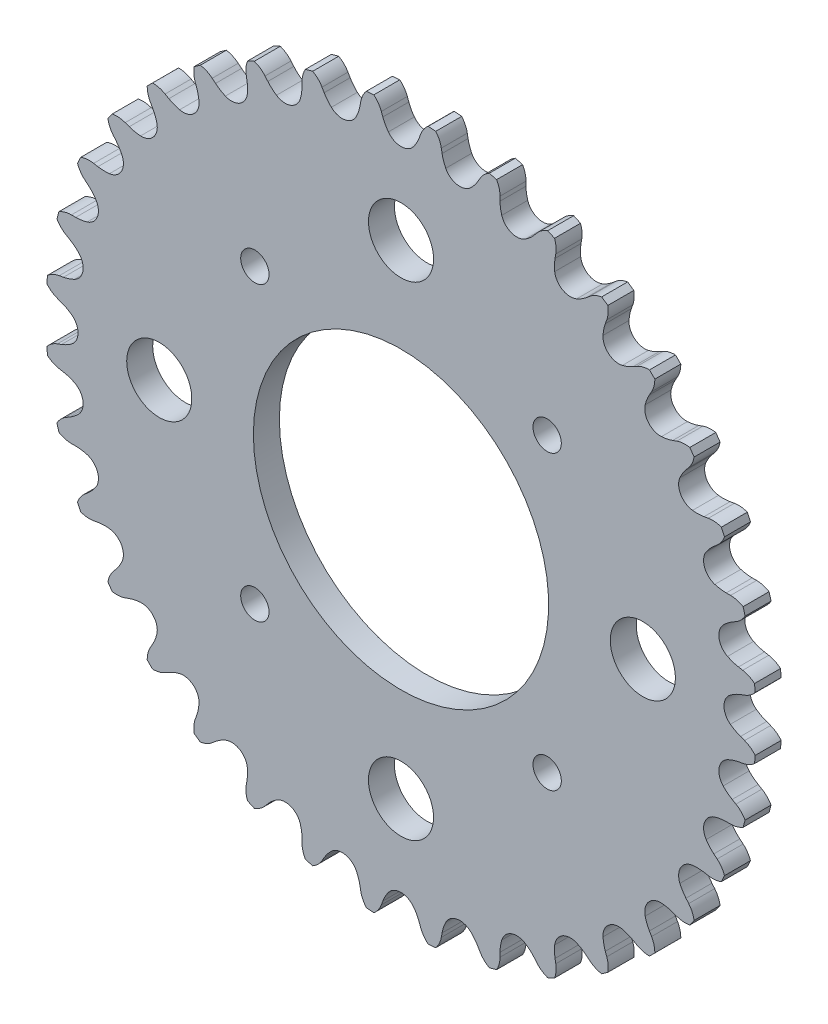
SolidWorks part; units mm, degrees
ref_plane "Front Plane" through (0, 0, 0) normal (0, 0, 1) x (1, 0, 0)
ref_plane "Top Plane" through (0, 0, 0) normal (0, 1, 0) x (1, 0, 0)
ref_plane "Right Plane" through (0, 0, 0) normal (1, 0, 0) x (0, 0, -1)
ref_axis "Axis1" through (0, 0, -88.99) along (0, 0, 1)
sketch "Sprocket-BaseSketch" plane through (0, 0, 0) normal (1, 0, 0) x (0, 0, -1)
  line L0 (1.397, 0) -> (1.397, 35.0204)
  line L1 (0.6032, 38.1954) -> (-0.6032, 38.1954)
  line L4 (-1.397, 35.0204) -> (-1.397, 0)
  line L5 (-1.397, 0) -> (1.397, 0)
  line L6 (5.588, 0) -> (-1.7463, 0) construction
  line L7 (-1.397, 35.0204) -> (-1.397, 38.1954)
  line L8 (-1.397, 38.1954) -> (-0.6032, 38.1954)
  line L9 (0.6032, 38.1954) -> (1.397, 38.1954)
  line L10 (1.397, 38.1954) -> (1.397, 35.0204)
  dimension "Hub Surface" = 1.397
  dimension "RightSide (1)" = 0.7938
  dimension "RightSide (2)" = 3.175
  dimension "LeftSide (1)" = 0.7938
  dimension "LeftSide (2)" = 3.175
  dimension "Tooth Width" = 2.794
revolve "25 (04C) ANSI (ISO) Chain Number, 2.868in P.D." add sketch "Sprocket-BaseSketch" angle 360 about L6
sketch "Tooth-Sketch" plane through (0, 0, 0) normal (0, 0, 1) x (1, 0, 0)
  line L0 (0, 0) -> (0, 48.5721) construction
  line L1 (1.9526, 36.5067) -> (2.1137, 36.9439)
  line L2 (-1.9526, 36.5067) -> (-2.1137, 36.9439)
  line L3 (0, 36.429) -> (6.3258, 35.8756) construction
  line L4 (0, 36.429) -> (-6.3258, 35.8756) construction
  arc A0 (-1.3615, 35.4154) -> (1.3615, 35.4154) centre (0, 36.429) ccw
  arc A1 (1.3615, 35.4154) -> (1.9526, 36.5067) centre (-2.1189, 38.0065) ccw
  arc A2 (-1.3615, 35.4154) -> (-1.9526, 36.5067) centre (2.1189, 38.0065) cw
  arc A3 (2.1137, 36.9439) -> (4.6052, 38.6813) centre (4.6052, 36.0261) cw
  arc A4 (-2.1137, 36.9439) -> (-4.6052, 38.6813) centre (-4.6052, 36.0261) ccw
  arc A5 (4.6052, 38.6813) -> (-4.6052, 38.6813) centre (0, 0) ccw
extrude "Tooth-Cut, Number of teeth: 36" cut sketch "Tooth-Sketch" against normal through all and the other way through all
pattern_circular "Tooth Pattern, 36 / 36" count 36 every 10 about axis through (0, 0, -88.99) along (0, 0, 1) of "Tooth-Cut, Number of teeth: 36"
sketch "Sketch1" plane through (0, 0, -1.397) normal (0, 0, -1) x (-1, 0, 0)
  line L0 (-15.7154, 15.7154) -> (0, 0) construction
  line L1 (0, 0) -> (0, 26) construction
  circle A0 centre (0, 0) radius 15.875
  circle A1 centre (-26.0031, 0.0002) radius 3.5
  circle A2 centre (-15.7154, 15.7154) radius 1.524
  circle A3 centre (15.7154, 15.7154) radius 1.524
  circle A4 centre (25.9969, -0.0006) radius 3.5
  circle A5 centre (15.7154, -15.7154) radius 1.524
  circle A6 centre (0.0006, 26.0031) radius 3.5
  circle A7 centre (-15.7154, -15.7154) radius 1.524
  circle A8 centre (0, 0) radius 17.5 construction
  circle A9 centre (26, 0) radius 3.2639 [skipped]
  circle A10 centre (-26, 0) radius 3.2639 [skipped]
  circle A11 centre (0, -26) radius 3.2639 [skipped]
  circle A12 centre (0, 26) radius 3.2639 [skipped]
  circle A13 centre (-0.0002, -26.0036) radius 3.5
  dimension "D1" = 31.75
  dimension "D4" = 3.048
  dimension "D7" = 4
  dimension "D2" = 45
  dimension "D5" = 22.225
  dimension "D6" = 26
extrude "Cut-Extrude1" cut sketch "Sketch1" against normal through all
